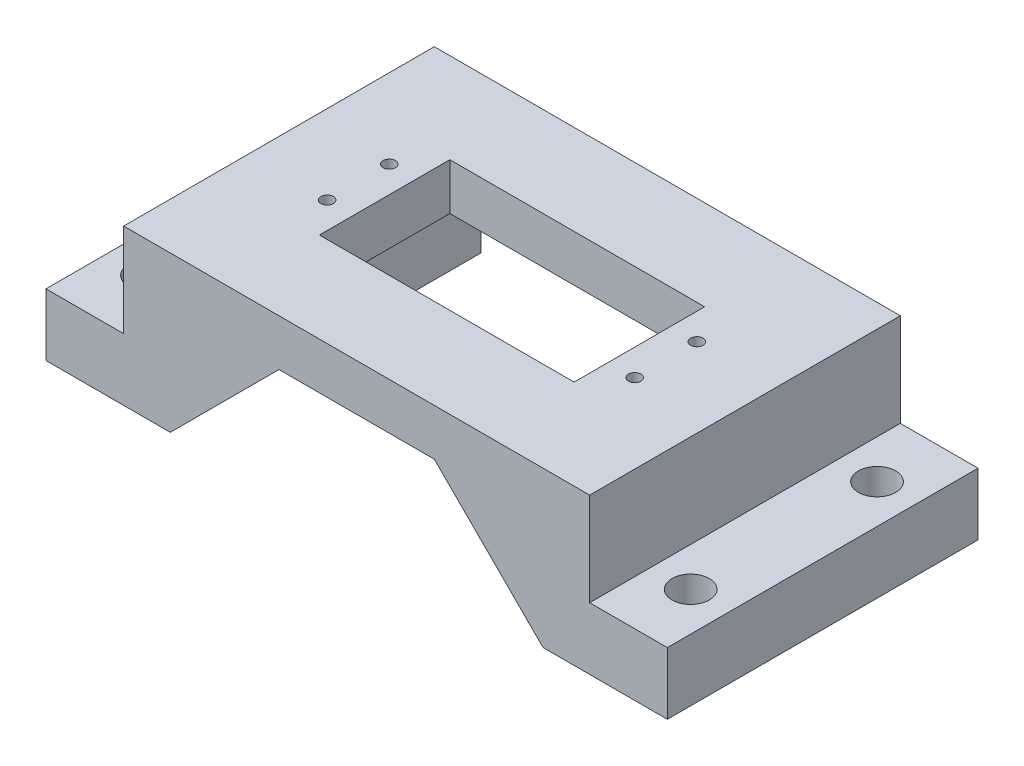
SolidWorks part; units mm, degrees
material "Thornel Mat VMA"
ref_plane "Front Plane" through (0, 0, 0) normal (0, 0, 1) x (1, 0, 0)
ref_plane "Top Plane" through (0, 0, 0) normal (0, 1, 0) x (1, 0, 0)
ref_plane "Right Plane" through (0, 0, 0) normal (1, 0, 0) x (0, 0, -1)
sketch "Sketch1" plane through (0, 0, 0) normal (0, 1, 0) x (1, 0, 0)
  line L0 (-100, 0) -> (100, 0) construction
  line L1 (-100, -30) -> (100, -30)
  line L2 (-100, -30) -> (-100, 30)
  line L3 (-100, 30) -> (100, 30)
  line L4 (100, -30) -> (100, 30)
  line L5 (-100, -30) -> (100, 30) construction
  line L6 (-100, 30) -> (100, -30) construction
  line L8 (-10.5, -20.5) -> (10.5, -20.5)
  line L9 (-10.5, -20.5) -> (-10.5, 20.5)
  line L10 (-10.5, 20.5) -> (10.5, 20.5)
  line L11 (10.5, -20.5) -> (10.5, 20.5)
  line L12 (-10.5, -20.5) -> (10.5, 20.5) construction
  line L13 (-10.5, 20.5) -> (10.5, -20.5) construction
  circle A0 centre (-5, -24.75) radius 1
  circle A1 centre (5, -24.75) radius 1
  circle A2 centre (5, 24.75) radius 1
  circle A3 centre (-5, 24.75) radius 1
  point P0 (0, 0)
  point P16 (0, 0)
  dimension "D5" = 2
  dimension "D1" = 200
  dimension "D2" = 60
  dimension "D3" = 10
  dimension "D4" = 5
  dimension "D6" = 24.75
  dimension "D7" = 21
  dimension "D8" = 41
extrude "Boss-Extrude1" [suppressed] add sketch "Sketch1" along normal blind 3
sketch "Sketch2" plane through (0, 0, 0) normal (0, 1, 0) x (1, 0, 0)
  line L1 (-50, -25) -> (50, -25)
  line L2 (-50, -25) -> (-50, 25)
  line L3 (-50, 25) -> (50, 25)
  line L4 (50, -25) -> (50, 25)
  line L5 (-50, -25) -> (50, 25) construction
  line L6 (-50, 25) -> (50, -25) construction
  line L7 (-30, -25) -> (30, -25)
  line L8 (-30, -25) -> (-30, 25)
  line L9 (-30, 25) -> (30, 25)
  line L10 (30, -25) -> (30, 25)
  line L11 (-30, -25) -> (30, 25) construction
  line L12 (-30, 25) -> (30, -25) construction
  point P0 (0, 0)
  point P6 (0, 0)
  dimension "D1" = 50
  dimension "D2" = 100
  dimension "D3" = 60
extrude "Boss-Extrude2" add sketch "Sketch2" along normal blind 10 contours L1 L8 L3 L2 | L10 L1 L4 L3 region at (-40, 0, 0) region at (40, 0, 0)
sketch "Sketch3" plane through (0, 10, 0) normal (0, 1, 0) x (1, 0, 0)
  line L0 (-50, -25) -> (-30, -25) construction
  line L1 (-30, 25) -> (-37.5, 25)
  line L2 (-30, 25) -> (-30, -25)
  line L3 (-30, -25) -> (-37.5, -25)
  line L4 (-37.5, 25) -> (-37.5, -25)
  line L5 (30, 25) -> (50, 25) construction
  line L6 (30, -25) -> (37.5, -25)
  line L7 (30, -25) -> (30, 25)
  line L8 (30, 25) -> (37.5, 25)
  line L9 (37.5, -25) -> (37.5, 25)
  dimension "D1" = 7.5
extrude "Boss-Extrude3" add sketch "Sketch3" along normal blind 15
sketch "Sketch4" plane through (30, 0, 0) normal (-1, 0, 0) x (0, 0, 1)
  line L0 (25, 25) -> (25, 10) construction
  line L1 (-25, 25) -> (25, 25)
  line L2 (-25, 25) -> (-25, 17.5)
  line L3 (-25, 17.5) -> (25, 17.5)
  line L4 (25, 25) -> (25, 17.5)
  dimension "D1" = 7.5
extrude "Boss-Extrude4" add sketch "Sketch4" along normal up to next
sketch "Sketch6" plane through (0, 25, 0) normal (0, 1, 0) x (1, 0, 0)
  line L0 (-37.5, -25) -> (37.5, -25) construction
  line L2 (0, 10.5) -> (0, -10.5) construction
  line L3 (20.5, -10.5) -> (20.5, 10.5)
  line L4 (20.5, -10.5) -> (-20.5, -10.5)
  line L5 (-20.5, -10.5) -> (-20.5, 10.5)
  line L6 (20.5, 10.5) -> (-20.5, 10.5)
  line L7 (20.5, -10.5) -> (-20.5, 10.5) construction
  line L8 (-20.5, -10.5) -> (20.5, 10.5) construction
  circle A2 centre (24.75, 5) radius 1
  circle A3 centre (24.75, -5) radius 1
  circle A4 centre (-24.75, 5) radius 1
  circle A5 centre (-24.75, -5) radius 1
  point P0 (0, 0)
  point P15 (0, 0)
  dimension "D3" = 5
  dimension "D2" = 2
  dimension "D1" = 10
  dimension "D4" = 24.75
  dimension "D5" = 21
  dimension "D6" = 41
extrude "Cut-Extrude1" cut sketch "Sketch6" against normal through all and the other way through all
hole_wizard "Ø6.0 (6) Diameter Hole1" positions "3DSketch2" profile "Sketch8" hole size "Ø6.0" standard "ANSI Metric" end condition up to next
sketch3d "3DSketch2"
  line L0 (-50, 10, 25) -> (-50, 10, -25) construction
  line L2 (50, 10, 25) -> (50, 10, -25) construction
  line L3 (-50, 10, -25) -> (-37.5, 10, -25) construction
  line L4 (-50, 10, 25) -> (-37.5, 10, 25) construction
  line L5 (37.5, 10, 25) -> (50, 10, 25) construction
  line L6 (37.5, 10, -25) -> (50, 10, -25) construction
  point P0 (-43.75, 10, -15)
  point P2 (-43.75, 10, 15)
  point P4 (43.75, 10, 15)
  point P6 (43.75, 10, -15)
  dimension "D1" = 6.25
  dimension "D2" = 6.25
  dimension "D3" = 6.25
  dimension "D4" = 6.25
  dimension "D5" = 10
  dimension "D6" = 10
  dimension "D7" = 10
  dimension "D8" = 10
sketch "Sketch8" plane through (-43.75, 10, -15) normal (1, 0, 0) x (0, 0, 1)
  line L0 (0, 0) -> (0, 10)
  line L1 (0, 10) -> (3, 10)
  line L2 (3, 10) -> (3, 0)
  line L5 (3, 0) -> (0, 0)
  line L11 (0, -6.35) -> (0, 107.95) construction
  dimension "Thru Hole Dia." = 6
  dimension "Thru Hole Depth" = 10
sketch "Sketch10" plane through (0, 17.5, 0) normal (0, -1, 0) x (1, 0, 0)
  line L1 (-30, 25) -> (-10, 25)
  line L2 (-30, 25) -> (-30, 15)
  line L3 (-30, 15) -> (-10, 15)
  line L4 (-10, 25) -> (-10, 15)
  line L5 (30, 25) -> (10, 25)
  line L6 (30, 25) -> (30, 15)
  line L7 (30, 15) -> (10, 15)
  line L8 (10, 25) -> (10, 15)
  dimension "D1" = 10
  dimension "D2" = 20
extrude "Boss-Extrude5" add sketch "Sketch10" along normal up to surface (17.5 mm away) up to face at (43.75, 0, 18)
chamfer "Chamfer1" distance 20 angle 45 2 edges at (10, 0, 20) (-10, 0, 20)
